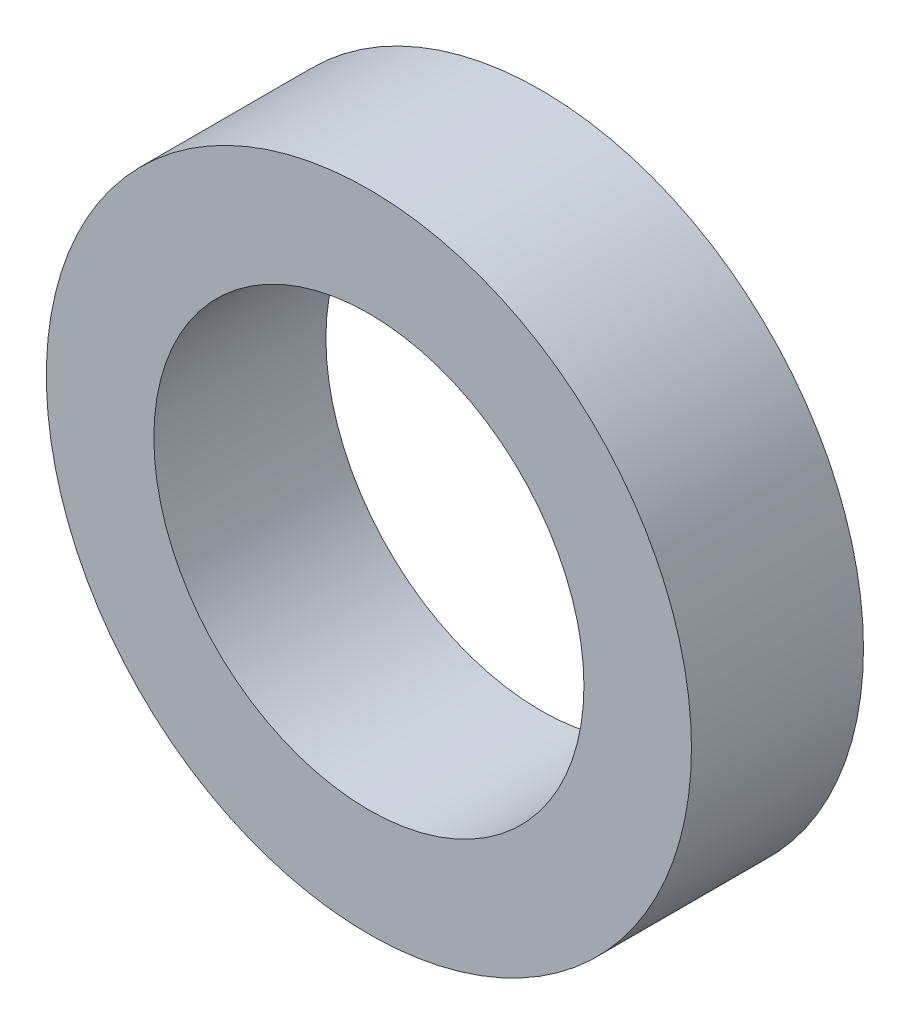
SolidWorks part; units mm, degrees
ref_plane "Front Plane" through (0, 0, 0) normal (0, 0, 1) x (1, 0, 0)
ref_plane "Top Plane" through (0, 0, 0) normal (0, 1, 0) x (1, 0, 0)
ref_plane "Right Plane" through (0, 0, 0) normal (1, 0, 0) x (0, 0, -1)
ref_axis "X" through (-88.99, 0, 0) along (1, 0, 0)
ref_axis "Y" through (0, 55, 0) along (0, -1, 0)
ref_axis "Z" through (0, 0, -88.99) along (0, 0, 1)
sketch "Sketch1" plane through (0, 0, 0) normal (0, 0, 1) x (1, 0, 0)
  circle A0 centre (0, 0) radius 5
  circle A1 centre (0, 0) radius 7.5
  dimension "D1" = 10
  dimension "D2" = 15
extrude "Boss-Extrude1" add sketch "Sketch1" along normal mid plane 4
